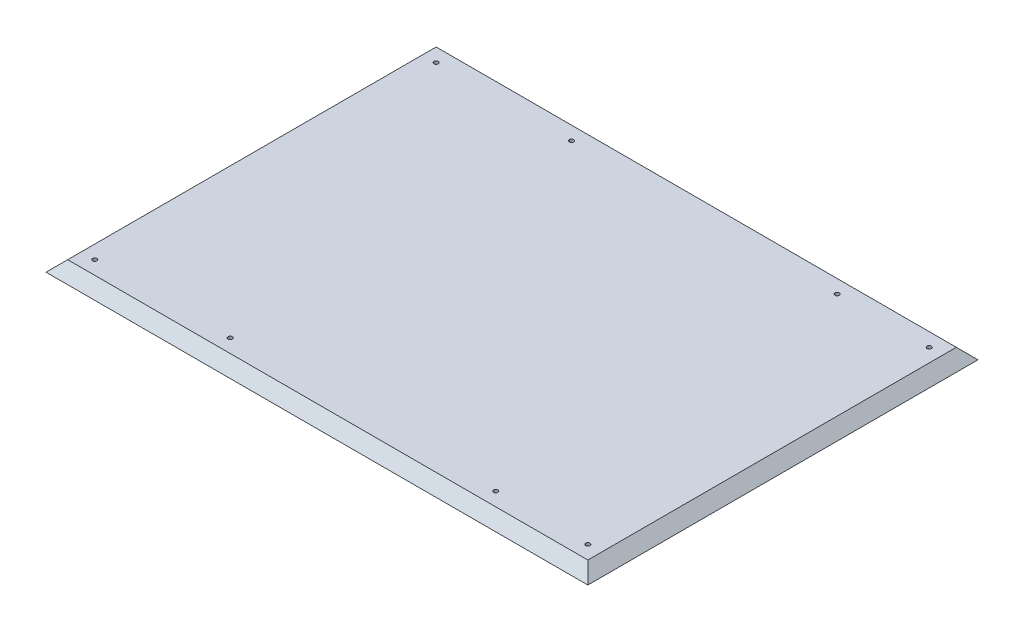
SolidWorks part; units mm, degrees
material "Kiefer"
ref_plane "Ebene vorne" through (0, 0, 0) normal (0, 0, 1) x (1, 0, 0)
ref_plane "Ebene oben" through (0, 0, 0) normal (0, 1, 0) x (1, 0, 0)
ref_plane "Ebene rechts" through (0, 0, 0) normal (1, 0, 0) x (0, 0, -1)
sketch "Skizze1" plane through (0, 0, 0) normal (0, 1, 0) x (1, 0, 0)
  line L1 (-250, 180) -> (250, 180)
  line L2 (-250, 180) -> (-250, -180)
  line L3 (-250, -180) -> (250, -180)
  line L4 (250, 180) -> (250, -180)
  line L5 (-250, 180) -> (250, -180) construction
  line L6 (-250, -180) -> (250, 180) construction
  point P0 (0, 0)
  dimension "D1" = 360
  dimension "D2" = 500
extrude "Aufsatz-Linear austragen1" add sketch "Skizze1" along normal blind 20
chamfer "Fase1" distance 10 distance2 10 8 edges at (0, 20, 180) (-250, 20, 0) (0, 20, -180) (250, 20, 0) (0, 0, -180) (-250, 0, 0) (0, 0, 180) (250, 0, 0)
sketch "Skizze3" plane through (0, 20, 0) normal (0, 1, 0) x (1, 0, 0)
  line L1 (-240, 170) -> (-240, -170) construction
  line L2 (240, -157.5) -> (-240, -157.5) construction
  line L3 (240, -157.5) -> (240, 157.5) construction
  line L4 (240, 157.5) -> (-240, 157.5) construction
  line L5 (-240, -157.5) -> (-240, 157.5) construction
  line L6 (240, -157.5) -> (-240, 157.5) construction
  line L8 (240, 157.5) -> (-240, -157.5) construction
  line L9 (240, 170) -> (-240, 170) construction
  line L10 (-102.5, 170) -> (-102.5, -170) construction
  line L11 (227.5, -170) -> (-227.5, -170) construction
  line L12 (227.5, -170) -> (227.5, 170) construction
  line L13 (227.5, 170) -> (-227.5, 170) construction
  line L14 (-227.5, -170) -> (-227.5, 170) construction
  line L15 (227.5, -170) -> (-227.5, 170) construction
  line L16 (227.5, 170) -> (-227.5, -170) construction
  line L17 (142.5, 170) -> (142.5, -170) construction
  circle A0 centre (-227.5, 157.5) radius 2
  circle A1 centre (-102.5, 157.5) radius 2
  circle A2 centre (142.5, 157.5) radius 2
  circle A3 centre (227.5, 157.5) radius 2
  circle A4 centre (227.5, -157.5) radius 2
  circle A5 centre (142.5, -157.5) radius 2
  circle A6 centre (-102.5, -157.5) radius 2
  circle A7 centre (-227.5, -157.5) radius 2
  point P0 (0, 0)
  point P10 (0, 0)
  dimension "D5" = 4
  dimension "D1" = 12.5
  dimension "D2" = 12.5
  dimension "D3" = 125
  dimension "D4" = 85
extrude "Schnitt-Linear austragen1" cut sketch "Skizze3" against normal through all
